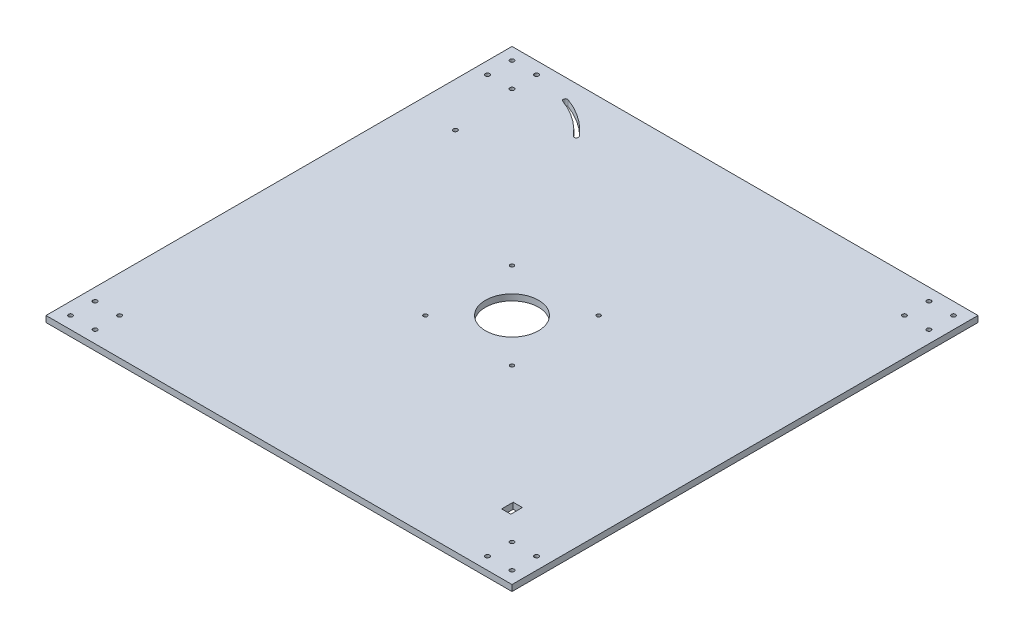
SolidWorks part; units mm, degrees
ref_plane "Front Plane" through (0, 0, 0) normal (0, 0, 1) x (1, 0, 0)
ref_plane "Top Plane" through (0, 0, 0) normal (0, 1, 0) x (1, 0, 0)
ref_plane "Right Plane" through (0, 0, 0) normal (1, 0, 0) x (0, 0, -1)
sketch "Sketch1" plane through (0, 0, 0) normal (0, 1, 0) x (1, 0, 0)
  line L1 (-241.3, -241.3) -> (241.3, -241.3)
  line L2 (-241.3, -241.3) -> (-241.3, 241.3)
  line L3 (-241.3, 241.3) -> (241.3, 241.3)
  line L4 (241.3, -241.3) -> (241.3, 241.3)
  line L5 (-241.3, -241.3) -> (241.3, 241.3) construction
  line L6 (-241.3, 241.3) -> (241.3, -241.3) construction
  point P0 (0, 0)
  dimension "D1" = 482.6
  dimension "D2" = 482.6
extrude "Boss-Extrude1" add sketch "Sketch1" along normal blind 6.35
sketch "Sketch2" plane through (0, 6.35, 0) normal (0, 1, 0) x (1, 0, 0)
  line L1 (-44.8437, -44.8437) -> (44.8437, -44.8437) construction
  line L2 (-44.8437, -44.8437) -> (-44.8437, 44.8437) construction
  line L3 (-44.8437, 44.8437) -> (44.8437, 44.8437) construction
  line L4 (44.8437, -44.8437) -> (44.8437, 44.8437) construction
  line L5 (-44.8437, -44.8437) -> (44.8437, 44.8437) construction
  line L6 (-44.8437, 44.8437) -> (44.8437, -44.8437) construction
  circle A0 centre (-44.8437, 44.8437) radius 1.9844
  circle A1 centre (44.8437, 44.8437) radius 1.9844
  circle A2 centre (-44.8437, -44.8437) radius 1.9844
  circle A3 centre (44.8437, -44.8437) radius 1.9844
  circle A4 centre (0, 0) radius 27.432
  point P0 (0, 0)
  dimension "D3" = 3.9688
  dimension "D4" = 54.864
  dimension "D1" = 89.6874
  dimension "D2" = 89.6874
extrude "Cut-Extrude1" cut sketch "Sketch2" against normal through all and the other way through all
sketch "Sketch3" plane through (0, 6.35, 0) normal (0, 1, 0) x (1, 0, 0)
  line L0 (177.6199, -166.8699) -> (168.1199, -178.8699) construction
  line L1 (0, 0) -> (241.3, -241.3) construction
  line L2 (168.1199, -166.8699) -> (177.6199, -178.8699) construction
  line L8 (168.1199, -178.8699) -> (177.6199, -178.8699)
  line L9 (168.1199, -178.8699) -> (168.1199, -166.8699)
  line L10 (168.1199, -166.8699) -> (177.6199, -166.8699)
  line L11 (177.6199, -178.8699) -> (177.6199, -166.8699)
  point P1 (0, 0)
  point P5 (172.8699, -172.8699)
  point P9 (172.8699, -172.8699)
  dimension "D1" = 244.475
  dimension "D2" = 9.5
  dimension "D3" = 12
extrude "Cut-Extrude2" cut sketch "Sketch3" against normal through all
sketch "Sketch4" plane through (0, 6.35, 0) normal (0, 1, 0) x (1, 0, 0)
  line L0 (241.3, 241.3) -> (-241.3, 241.3) construction
  line L1 (-215.9, 215.9) -> (215.9, 215.9) construction
  line L2 (-215.9, 215.9) -> (-215.9, -215.9) construction
  line L3 (-215.9, -215.9) -> (215.9, -215.9) construction
  line L4 (215.9, 215.9) -> (215.9, -215.9) construction
  line L5 (-215.9, 215.9) -> (215.9, -215.9) construction
  line L6 (-215.9, -215.9) -> (215.9, 215.9) construction
  line L7 (-241.3, 241.3) -> (-241.3, -241.3) construction
  line L9 (-228.6, 228.6) -> (-203.2, 228.6) construction
  line L10 (-228.6, 228.6) -> (-228.6, 203.2) construction
  line L11 (-228.6, 203.2) -> (-203.2, 203.2) construction
  line L12 (-203.2, 228.6) -> (-203.2, 203.2) construction
  line L13 (-228.6, 228.6) -> (-203.2, 203.2) construction
  line L14 (-228.6, 203.2) -> (-203.2, 228.6) construction
  line L15 (-228.6, -228.6) -> (-203.2, -228.6) construction
  line L16 (-228.6, -228.6) -> (-228.6, -203.2) construction
  line L17 (-228.6, -203.2) -> (-203.2, -203.2) construction
  line L18 (-203.2, -228.6) -> (-203.2, -203.2) construction
  line L19 (-228.6, -228.6) -> (-203.2, -203.2) construction
  line L20 (-228.6, -203.2) -> (-203.2, -228.6) construction
  line L21 (228.6, -228.6) -> (203.2, -228.6) construction
  line L22 (228.6, -228.6) -> (228.6, -203.2) construction
  line L23 (228.6, -203.2) -> (203.2, -203.2) construction
  line L24 (203.2, -228.6) -> (203.2, -203.2) construction
  line L25 (228.6, -228.6) -> (203.2, -203.2) construction
  line L26 (228.6, -203.2) -> (203.2, -228.6) construction
  line L27 (228.6, 228.6) -> (203.2, 228.6) construction
  line L28 (228.6, 228.6) -> (228.6, 203.2) construction
  line L29 (228.6, 203.2) -> (203.2, 203.2) construction
  line L30 (203.2, 228.6) -> (203.2, 203.2) construction
  line L31 (228.6, 228.6) -> (203.2, 203.2) construction
  line L32 (228.6, 203.2) -> (203.2, 228.6) construction
  circle A0 centre (-228.6, 228.6) radius 2.1828
  circle A1 centre (-203.2, 228.6) radius 2.1828
  circle A2 centre (-228.6, 203.2) radius 2.1828
  circle A3 centre (-203.2, 203.2) radius 2.1828
  circle A4 centre (203.2, 228.6) radius 2.1828
  circle A5 centre (203.2, 203.2) radius 2.1828
  circle A6 centre (228.6, 203.2) radius 2.1828
  circle A7 centre (228.6, 228.6) radius 2.1828
  circle A8 centre (203.2, -203.2) radius 2.1828
  circle A9 centre (228.6, -203.2) radius 2.1828
  circle A10 centre (228.6, -228.6) radius 2.1828
  circle A11 centre (203.2, -228.6) radius 2.1828
  circle A12 centre (-228.6, -203.2) radius 2.1828
  circle A13 centre (-203.2, -203.2) radius 2.1828
  circle A14 centre (-203.2, -228.6) radius 2.1828
  circle A15 centre (-228.6, -228.6) radius 2.1828
  point P0 (0, 0)
  dimension "D4" = 4.3656
  dimension "D1" = 25.4
  dimension "D2" = 25.4
  dimension "D3" = 25.4
extrude "Cut-Extrude3" cut sketch "Sketch4" against normal through all
sketch "Sketch5" plane through (0, 6.35, 0) normal (0, 1, 0) x (1, 0, 0)
  line L0 (0, 0) -> (-268.4034, 187.9381) construction
  line L1 (-127.4794, 194.0909) -> (-195.5807, 136.9471) construction
  line L2 (-165.1752, 220.4858) -> (-195.5807, 136.9471) construction
  line L3 (0, 0) -> (0, 241.3) construction
  line L4 (241.3, 241.3) -> (-241.3, 241.3) construction
  circle A0 centre (-195.5807, 136.9471) radius 2.1828
  circle A1 centre (-195.5807, 136.9471) radius 88.9 construction
  arc A2 (-165.1752, 220.4858) -> (-127.4794, 194.0909) centre (-195.5807, 136.9471) cw construction
  arc A3 (-125.8073, 195.494) -> (-164.4286, 222.537) centre (-195.5807, 136.9471) ccw
  arc A4 (-129.1515, 192.6878) -> (-165.9217, 218.4346) centre (-195.5807, 136.9471) ccw
  arc A5 (-129.1515, 192.6878) -> (-125.8073, 195.494) centre (-127.4794, 194.0909) ccw
  arc A6 (-164.4286, 222.537) -> (-165.9217, 218.4346) centre (-165.1752, 220.4858) ccw
  point P7 (-144.5898, 209.7697)
  dimension "D1" = 177.8
  dimension "D2" = 4.3656
  dimension "D3" = 30
  dimension "D6" = 2.1828
  dimension "D4" = 238.76
  dimension "D5" = 75
  dimension "D7" = 55
extrude "Cut-Extrude4" cut sketch "Sketch5" against normal through all
